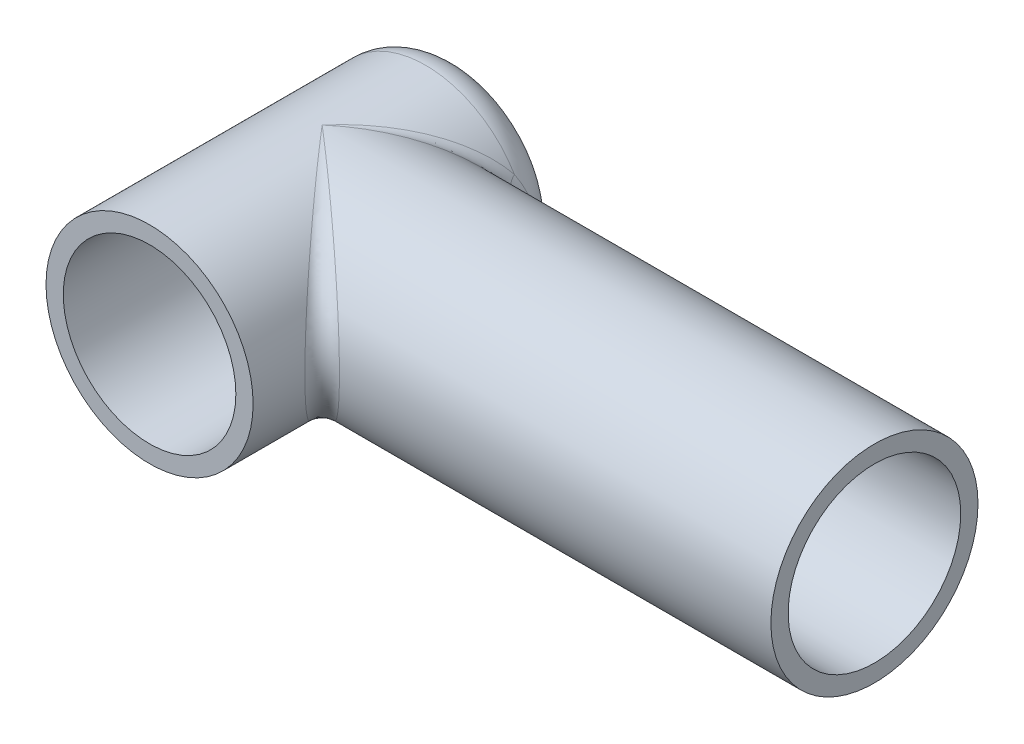
SolidWorks part; units mm, degrees
ref_plane "Front Plane" through (0, 0, 0) normal (0, 0, 1) x (1, 0, 0)
ref_plane "Top Plane" through (0, 0, 0) normal (0, 1, 0) x (1, 0, 0)
ref_plane "Right Plane" through (0, 0, 0) normal (1, 0, 0) x (0, 0, -1)
sketch "Sketch1" plane through (0, 0, 0) normal (0, 1, 0) x (1, 0, 0)
  line L0 (0, 0) -> (0, -80) construction
  line L1 (0, -30) -> (160, -30) construction
  dimension "D1" = 80
  dimension "D2" = 160
  dimension "D3" = 30
ref_plane "Plane1" through (0, 0, 80) normal (0, 0, 1) x (1, 0, 0)
sketch "Sketch2" plane through (0, 0, 80) normal (0, 0, 1) x (1, 0, 0)
  circle A0 centre (0, 0) radius 30
  circle A1 centre (0, 0) radius 25
extrude "Boss-Extrude1" add sketch "Sketch2" against normal up to vertex (80 mm away) up to point (0, 0, 0)
ref_plane "Plane2" through (160, 0, 30) normal (1, 0, 0) x (0, 0, -1)
sketch "Sketch3" plane through (160, 0, 30) normal (1, 0, 0) x (0, 0, -1)
  circle A0 centre (0, 0) radius 30
  circle A1 centre (0, 0) radius 25
extrude "Boss-Extrude3" add sketch "Sketch3" against normal up to surface (130 mm away) up to face at (30, 0, 0)
ref_plane "Plane3" through (0, 0, 0) normal (0, 0, 1) x (1, 0, 0)
sketch "Sketch4" plane through (0, 0, 0) normal (0, 0, 1) x (1, 0, 0)
  circle A0 centre (0, 0) radius 30
extrude "Boss-Extrude4" add sketch "Sketch4" against normal blind 10
fillet "Fillet1" radius 10 1 edges at (30, 0, -10)
fillet "Fillet2" radius 5 3 edges at (21.2132, 21.2132, 8.7868) (21.2132, -21.2132, 8.7868) (30, 0, 60)
